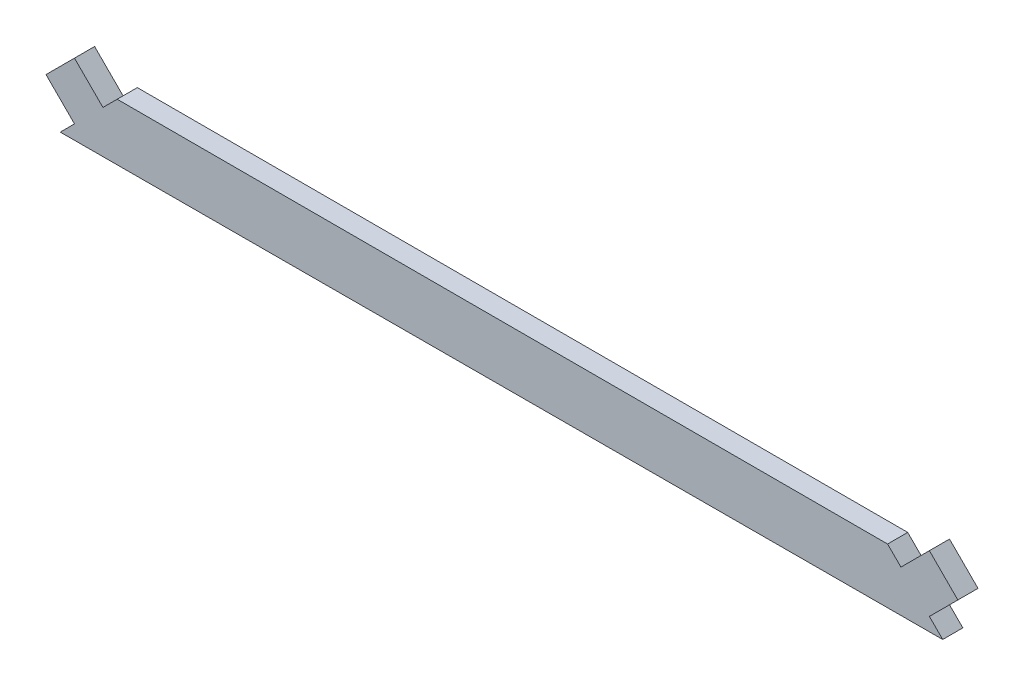
SolidWorks part; units mm, degrees
ref_plane "Front Plane" through (0, 0, 0) normal (0, 0, 1) x (1, 0, 0)
ref_plane "Top Plane" through (0, 0, 0) normal (0, 1, 0) x (1, 0, 0)
ref_plane "Right Plane" through (0, 0, 0) normal (1, 0, 0) x (0, 0, -1)
sketch "Sketch1" plane through (0, 0, 0) normal (0, 0, 1) x (1, 0, 0)
  line L0 (-139.4438, -165.8849) -> (138.8703, -165.3114)
  line L1 (0, -26.4411) -> (49.3856, -75.8267) construction
  line L2 (138.8703, -165.3114) -> (121.4833, -147.9244)
  line L3 (121.4833, -147.9244) -> (-121.4833, -147.9244)
  line L4 (-139.4438, -165.8849) -> (-121.2335, -147.6746) construction
  line L5 (-121.4833, -147.9244) -> (-139.4438, -165.8849)
  arc A0 (138.8703, -165.3114) -> (-138.8703, -165.3114) centre (0, 0) ccw construction
  dimension "D1" = 25.4
extrude "Boss-Extrude1" add sketch "Sketch1" along normal mid plane 6.35
sketch "Sketch2" plane through (0, 0, -3.175) normal (0, 0, -1) x (-1, 0, 0)
  line L0 (-130.1768, -156.6179) -> (-127.0422, -159.7525) construction
  line L1 (-138.8703, -165.3114) -> (-121.4833, -147.9244) construction
  line L2 (-125.6867, -152.1278) -> (-134.6669, -143.1475)
  line L3 (-134.6669, -143.1475) -> (-143.6472, -152.1278)
  line L4 (-143.6472, -152.1278) -> (-134.6669, -161.108)
  line L8 (-121.4833, -147.9244) -> (-125.6867, -152.1278)
  line L12 (139.4438, -165.8849) -> (121.4833, -147.9244)
  line L13 (121.4833, -147.9244) -> (-121.4833, -147.9244)
  line L14 (-121.4833, -147.9244) -> (-138.8703, -165.3114)
  line L15 (-138.8703, -165.3114) -> (139.4438, -165.8849)
  line L16 (139.4438, -165.8849) -> (121.4833, -147.9244)
  line L17 (121.4833, -147.9244) -> (-121.4833, -147.9244)
  line L18 (-134.6669, -161.108) -> (-138.8703, -165.3114)
  line L19 (-138.8703, -165.3114) -> (139.4438, -165.8849)
  dimension "D1" = 12.7
  dimension "D2" = 12.7
  dimension "D3" = 0
extrude "Boss-Extrude2" add sketch "Sketch2" against normal up to surface (6.35 mm away) up to face at (-0.1434, -156.7613, 3.175)
sketch "Sketch3" plane through (0, 0, -3.175) normal (0, 0, -1) x (-1, 0, 0)
  line L0 (130.4636, -156.9046) -> (137.1973, -150.1709) construction
  line L1 (121.4833, -147.9244) -> (139.4438, -165.8849) construction
  line L2 (125.9734, -152.4145) -> (134.9537, -143.4343)
  line L3 (134.9537, -143.4343) -> (143.9339, -152.4145)
  line L4 (143.9339, -152.4145) -> (134.9537, -161.3948)
  line L13 (139.4438, -165.8849) -> (121.4833, -147.9244)
  line L14 (121.4833, -147.9244) -> (-121.4833, -147.9244)
  line L15 (-121.4833, -147.9244) -> (-125.6867, -152.1278)
  line L16 (-125.6867, -152.1278) -> (-134.6669, -143.1475)
  line L17 (-134.6669, -143.1475) -> (-143.6472, -152.1278)
  line L18 (-143.6472, -152.1278) -> (-134.6669, -161.108)
  line L19 (-134.6669, -161.108) -> (-138.8703, -165.3114)
  line L20 (-138.8703, -165.3114) -> (139.4438, -165.8849)
  line L21 (134.9537, -161.3948) -> (125.9734, -152.4145)
  dimension "D1" = 12.7
  dimension "D2" = 12.7
  dimension "D3" = 0
extrude "Boss-Extrude4" add sketch "Sketch3" against normal blind 6.35
